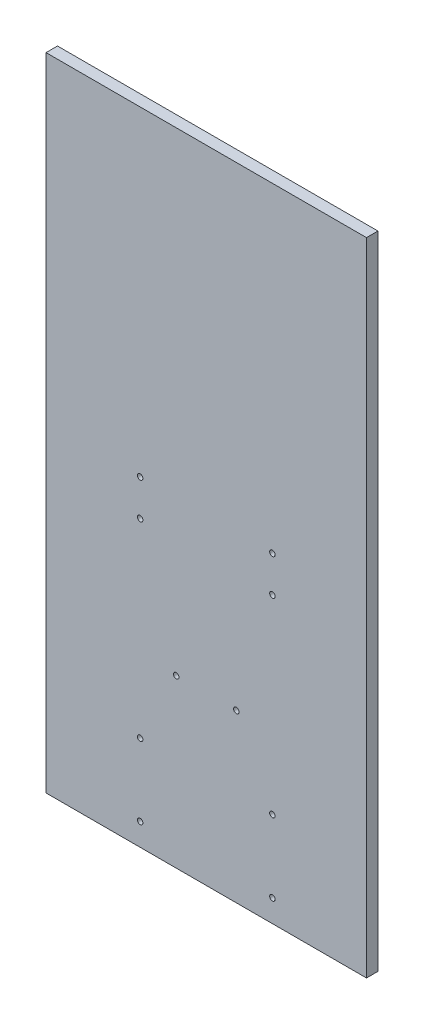
SolidWorks part; units mm, degrees
material "Beech"
ref_plane "Front Plane" through (0, 0, 0) normal (0, 0, 1) x (1, 0, 0)
ref_plane "Top Plane" through (0, 0, 0) normal (0, 1, 0) x (1, 0, 0)
ref_plane "Right Plane" through (0, 0, 0) normal (1, 0, 0) x (0, 0, -1)
sketch "Sketch1" plane through (0, 0, 0) normal (0, 0, 1) x (1, 0, 0)
  line L8 (266.573, 7002.78) -> (-266.573, 7002.78)
  line L9 (-266.573, 7002.78) -> (-266.573, 5935.98)
  line L10 (-266.573, 5935.98) -> (266.573, 5935.98)
  line L11 (266.573, 5935.98) -> (266.573, 7002.78)
  point P2 (0, 7002.78)
  dimension "D1" = 1066.8
  dimension "D2" = 533.146
extrude "Boss-Extrude1" add sketch "Sketch1" against normal blind 19.05
hole_wizard "23/64 (0.35938) Diameter Hole1" positions "Sketch2" profile "Sketch3" hole size "23/64" standard "ANSI Inch" end condition through all
sketch "Sketch2" plane through (0, 0, -19.05) normal (0, 0, -1) x (-1, 0, 0)
  point P15 (110, 5973.262)
  point P18 (110, 6093.262)
  point P21 (-110, 6093.262)
  point P24 (-110, 5973.262)
  point P27 (-50, 6213.262)
  point P30 (50, 6213.262)
  point P33 (-110, 6409.662)
  point P36 (-110, 6469.662)
  point P39 (110, 6409.662)
  point P42 (110, 6469.662)
sketch "Sketch3" plane through (-110, 5973.262, -19.05) normal (1, 0, 0) x (0, 1, 0)
  line L0 (0, 0) -> (0, 19.05)
  line L1 (0, 19.05) -> (4.5641, 19.05)
  line L2 (4.5641, 19.05) -> (4.5641, 0)
  line L5 (4.5641, 0) -> (0, 0)
  line L11 (0, -6.35) -> (0, 107.95) construction
  dimension "Thru Hole Dia." = 9.1283
  dimension "Thru Hole Depth" = 19.05
sketch "Sketch4" plane through (0, 0, 0) normal (0, 0, 1) x (1, 0, 0)
  line L0 (-266.573, 7002.78) -> (-266.573, 5935.98) construction
  line L1 (-266.573, 5935.98) -> (-222.123, 5935.98)
  line L2 (-266.573, 5935.98) -> (-266.573, 6012.18)
  line L3 (-266.573, 6012.18) -> (-222.123, 6012.18)
  line L4 (-222.123, 5935.98) -> (-222.123, 6012.18)
  line L5 (-266.573, 7002.78) -> (-222.123, 7002.78)
  line L6 (-266.573, 7002.78) -> (-266.573, 6926.58)
  line L7 (-266.573, 6926.58) -> (-222.123, 6926.58)
  line L8 (-222.123, 7002.78) -> (-222.123, 6926.58)
  line L9 (266.573, 7002.78) -> (-266.573, 7002.78) construction
  line L10 (266.573, 5935.98) -> (266.573, 7002.78) construction
  line L11 (266.573, 7002.78) -> (222.123, 7002.78)
  line L12 (266.573, 7002.78) -> (266.573, 6926.58)
  line L13 (266.573, 6926.58) -> (222.123, 6926.58)
  line L14 (222.123, 7002.78) -> (222.123, 6926.58)
  line L15 (-266.573, 5935.98) -> (266.573, 5935.98) construction
  line L16 (266.573, 5935.98) -> (222.123, 5935.98)
  line L17 (266.573, 5935.98) -> (266.573, 6012.18)
  line L18 (266.573, 6012.18) -> (222.123, 6012.18)
  line L19 (222.123, 5935.98) -> (222.123, 6012.18)
  point P22 (-266.573, 5935.98)
  point P23 (-266.573, 5935.98)
  point P26 (266.573, 5935.98)
  dimension "D1" = 76.2
  dimension "D2" = 44.45
split line "Split Line1" [suppressed]
